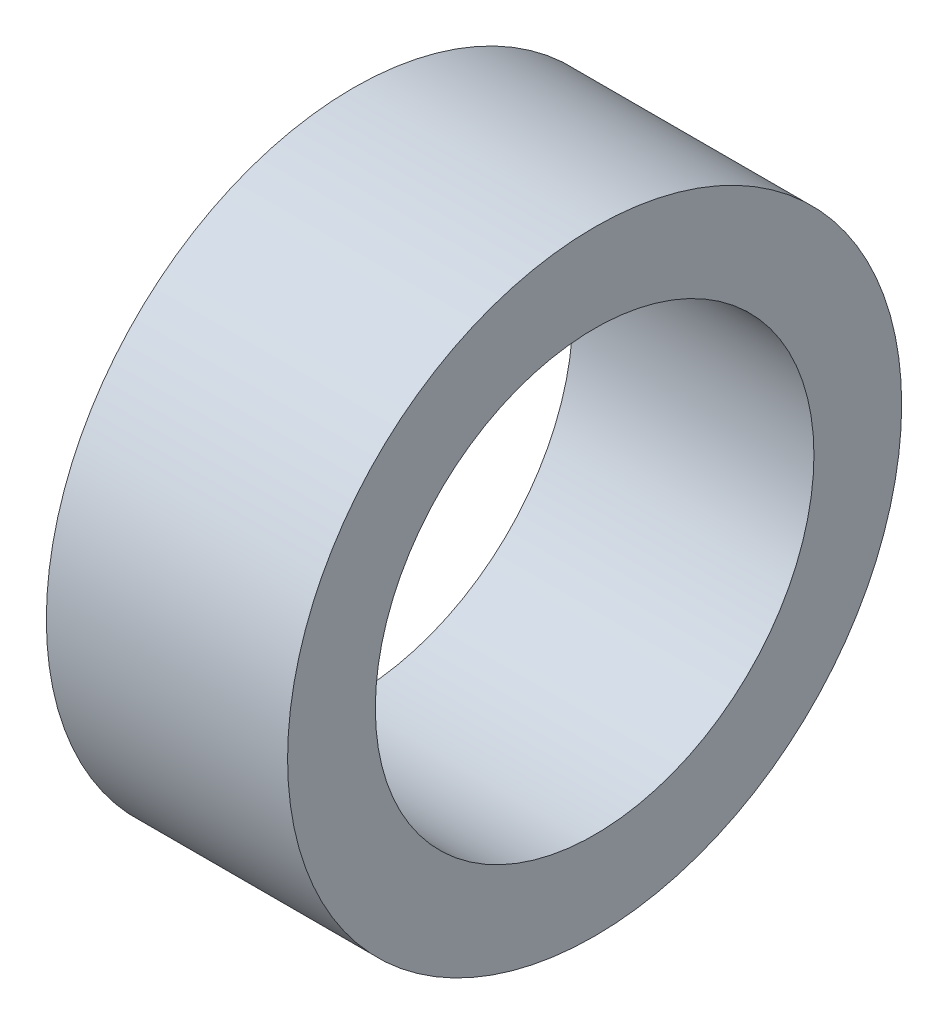
SolidWorks part; units mm, degrees
ref_plane "Front Plane" through (0, 0, 0) normal (0, 0, 1) x (1, 0, 0)
ref_plane "Top Plane" through (0, 0, 0) normal (0, 1, 0) x (1, 0, 0)
ref_plane "Right Plane" through (0, 0, 0) normal (1, 0, 0) x (0, 0, -1)
sketch "Sketch1" plane through (0, 0, 0) normal (0, 0, 1) x (1, 0, 0)
  line L0 (21, 7) -> (21, 5)
  line L1 (21, 5) -> (26.5, 5)
  line L2 (26.5, 5) -> (26.5, 7)
  line L3 (26.5, 7) -> (21, 7)
  line L4 (21, 0) -> (26.5, 0) construction
revolve "Revolve1" add sketch "Sketch1" angle 360 about L4 reverse direction yes
